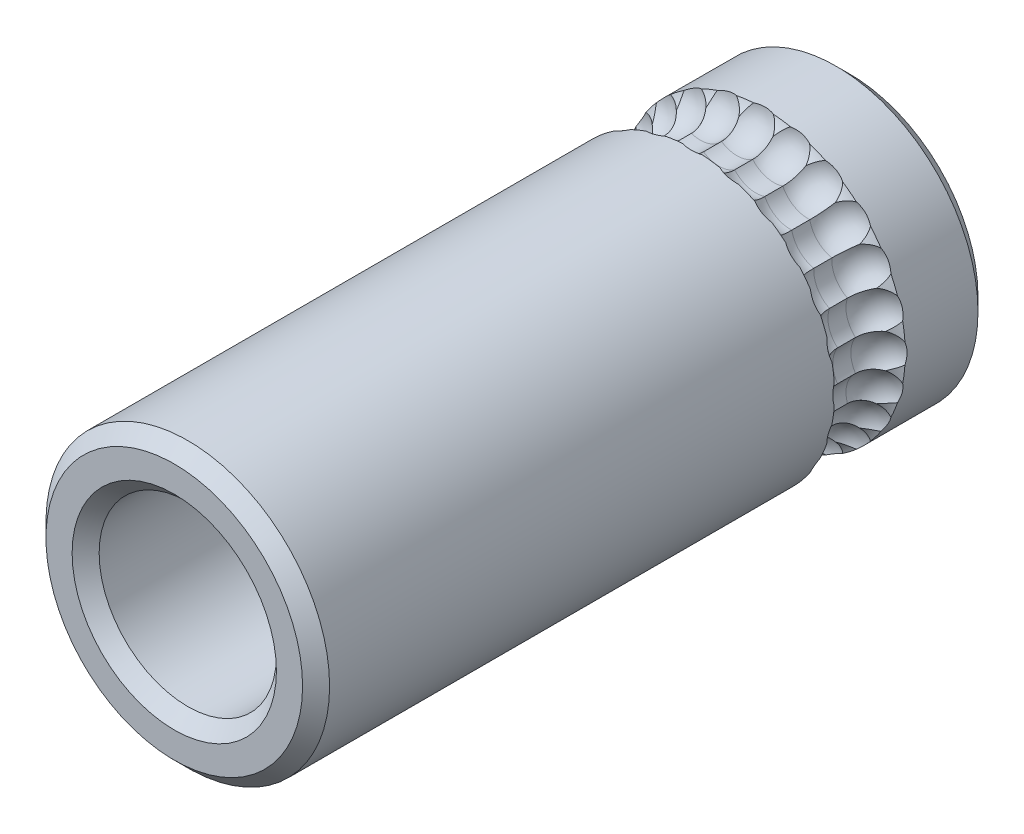
SolidWorks part; units mm, degrees
ref_plane "Front Plane" through (0, 0, 0) normal (0, 0, 1) x (1, 0, 0)
ref_plane "Top Plane" through (0, 0, 0) normal (0, 1, 0) x (1, 0, 0)
ref_plane "Right Plane" through (0, 0, 0) normal (1, 0, 0) x (0, 0, -1)
sketch "Sketch1" plane through (0, 0, 0) normal (0, 0, 1) x (1, 0, 0)
  circle A0 centre (0, 0) radius 2.5
  circle A1 centre (0, 0) radius 4
  dimension "D1" = 5
  dimension "D2" = 8
extrude "Boss-Extrude1" add sketch "Sketch1" along normal blind 19.05
sketch "Sketch3" plane through (0, 0, 0) normal (0, 1, 0) x (1, 0, 0)
  line L0 (4, -3.175) -> (4, -3.683) construction
  line L1 (4, -19.05) -> (4, 0) construction
  line L3 (3.2063, -3.175) -> (3.2063, -3.683)
  line L4 (4, 0) -> (-4, 0) construction
  line L5 (4, -2.3812) -> (4, -4.4768)
  arc A0 (4, -2.3812) -> (3.2063, -3.175) centre (4, -3.175) ccw
  arc A1 (3.2063, -3.683) -> (4, -4.4768) centre (4, -3.683) ccw
  point P4 (4, -3.429)
  dimension "D1" = 0.7937
  dimension "D2" = 0.508
  dimension "D3" = 3.175
revolve "Cut-Revolve2" cut sketch "Sketch3" angle 360 about L0
pattern_circular "CirPattern1" count 24 over 360 about axis through (0, 0, 19.05) along (0, 0, -1) of "Cut-Revolve2"
sketch "Sketch4" plane through (0, 0, 0) normal (0, 1, 0) x (1, 0, 0)
  line L0 (4.2794, -3.175) -> (4.2794, -3.683) construction
  line L1 (5.0731, -3.175) -> (5.0731, -3.683)
  line L2 (3.4857, -3.175) -> (3.4857, -3.683)
  line L3 (3.3391, -3.175) -> (3.07, -3.175) construction
  line L4 (3.3391, -3.683) -> (3.07, -3.683) construction
  line L5 (4, -19.05) -> (4, -4.4768) construction
  arc A0 (5.0731, -3.175) -> (3.4857, -3.175) centre (4.2794, -3.175) ccw
  arc A1 (3.4857, -3.683) -> (5.0731, -3.683) centre (4.2794, -3.683) ccw
  point P2 (4.2794, -3.429)
  dimension "D1" = 0.7937
  dimension "D2" = 0.2794
ref_axis "Axis1" through (0, 0, 19.05) along (0, 0, -1)
revolve "Cut-Revolve3" cut sketch "Sketch4" angle 360 about axis through (0, 0, 19.05) along (0, 0, -1)
chamfer "Chamfer1" distance 0.381 angle 45 4 edges at (4, 0, 0) (4, 0, 19.05) (2.5, 0, 19.05) (2.5, 0, 0)
sketch "Sketch5" plane through (0, 0, 0) normal (0, 1, 0) x (1, 0, 0)
  line L0 (0, -19.05) -> (0, 0) construction
  line L1 (-3.619, -19.05) -> (3.619, -19.05) construction
  circle A0 centre (0, -9.525) radius 1.397
  circle A1 centre (0, -14.2875) radius 1.397
  dimension "D1" = 2.794
  dimension "D2" = 4.7625
  dimension "D3" = 4.7625
extrude "Cut-Extrude1" cut sketch "Sketch5" against normal up to next
